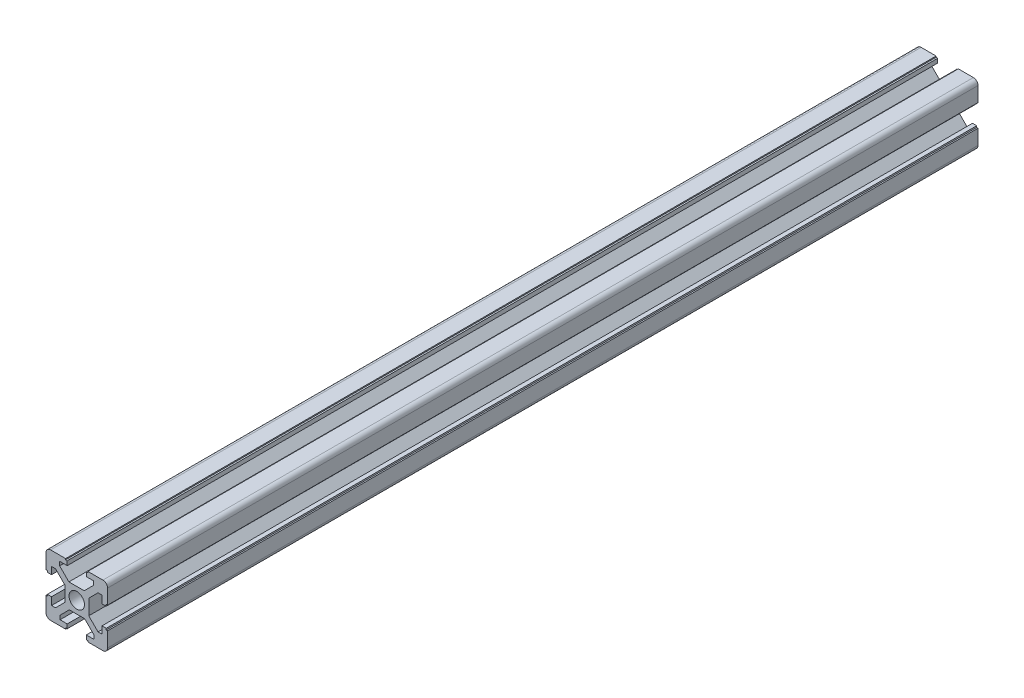
SolidWorks part; units mm, degrees
ref_plane "Front Plane" through (0, 0, 0) normal (0, 0, 1) x (1, 0, 0)
ref_plane "Top Plane" through (0, 0, 0) normal (0, 1, 0) x (1, 0, 0)
ref_plane "Right Plane" through (0, 0, 0) normal (1, 0, 0) x (0, 0, -1)
sketch "Sketch1" plane through (0, 0, 0) normal (0, 0, 1) x (1, 0, 0)
  line L0 (240.9169, 601.7923) -> (1204.5843, 601.7923) construction
  line L6 (13.0291, 10.3872) -> (13.0291, 12.8554)
  line L7 (12.7291, 6.0212) -> (29.7291, 6.0212)
  line L11 (11.2291, 7.5212) -> (11.2291, 24.3895)
  line L12 (12.7291, 25.8895) -> (29.7291, 25.8895)
  line L13 (31.2291, 7.5212) -> (31.2291, 24.3895)
  line L14 (11.2291, 6.0212) -> (31.2291, 25.8895) construction
  line L15 (11.2291, 25.8895) -> (31.2291, 6.0212) construction
  line L16 (13.0291, 24.0895) -> (13.041, 24.0895)
  line L17 (29.4291, 10.5205) -> (29.4291, 12.8554)
  line L18 (13.0291, 7.8212) -> (13.041, 7.8212)
  line L19 (11.2291, 15.9554) -> (31.2291, 15.9554) construction
  line L20 (11.6567, 12.8554) -> (13.0291, 12.8554)
  line L21 (11.6567, 19.0554) -> (13.0291, 19.0554)
  line L22 (21.2291, 6.0212) -> (21.2291, 25.8895) construction
  line L23 (24.8338, 25.9554) -> (24.8338, 25.5277)
  line L24 (17.3291, 21.0535) -> (17.3291, 19.8297)
  line L25 (11.2291, 19.56) -> (11.6567, 19.56)
  line L26 (11.6567, 19.56) -> (11.6567, 19.0554)
  line L27 (11.6567, 19.0554) -> (13.0291, 19.0554)
  line L28 (17.3291, 18.3778) -> (14.3166, 21.3903)
  line L29 (14.3166, 21.3903) -> (13.0291, 21.3903)
  line L30 (17.3291, 13.3997) -> (14.3166, 10.3872)
  line L31 (14.3166, 10.3872) -> (13.0291, 10.3872)
  line L32 (13.0291, 7.8212) -> (13.0291, 24.0895) construction
  line L33 (29.4172, 7.8212) -> (29.4291, 7.8212)
  line L34 (13.0291, 7.8212) -> (29.4291, 7.8212) construction
  line L35 (17.3291, 12.081) -> (17.3291, 10.641)
  line L36 (24.8338, 25.5277) -> (24.3291, 25.5277)
  line L37 (11.2291, 12.8554) -> (31.2291, 12.8554) construction
  line L38 (24.3291, 25.5277) -> (24.3291, 24.1554)
  line L39 (11.2291, 19.0554) -> (31.2291, 19.0554) construction
  line L40 (17.3291, 18.3778) -> (17.3291, 13.3997)
  line L41 (11.6567, 12.8554) -> (11.6567, 12.3367)
  line L42 (11.6567, 12.3367) -> (11.2291, 12.3367)
  line L43 (13.0291, 19.0554) -> (13.0291, 21.3903)
  line L44 (24.3291, 24.1554) -> (26.664, 24.1554)
  line L45 (26.664, 22.8679) -> (26.664, 24.1554)
  line L46 (23.6515, 19.8554) -> (26.664, 22.8679)
  line L47 (23.6515, 19.8554) -> (18.6734, 19.8554)
  line L48 (18.6734, 19.8554) -> (15.661, 22.8679)
  line L49 (15.661, 24.1554) -> (18.1291, 24.1554)
  line L50 (15.661, 22.8679) -> (15.661, 24.1554)
  line L51 (18.1291, 25.5277) -> (18.1291, 24.1554)
  line L52 (18.1291, 25.5277) -> (17.6104, 25.5277)
  line L53 (17.6104, 25.5277) -> (17.6104, 25.9554)
  line L54 (31.2291, 12.3507) -> (30.8015, 12.3507)
  line L55 (30.8015, 12.3507) -> (30.8015, 12.8554)
  line L56 (30.8015, 12.8554) -> (29.4291, 12.8554)
  line L57 (29.4291, 12.8554) -> (29.4291, 10.5205)
  line L58 (28.1416, 10.5205) -> (29.4291, 10.5205)
  line L59 (25.1291, 13.533) -> (28.1416, 10.5205)
  line L60 (25.1291, 13.533) -> (25.1291, 18.511)
  line L61 (25.1291, 18.511) -> (28.1416, 21.5235)
  line L62 (29.4291, 21.5235) -> (29.4291, 19.0554)
  line L63 (28.1416, 21.5235) -> (29.4291, 21.5235)
  line L64 (30.8015, 19.0554) -> (29.4291, 19.0554)
  line L65 (30.8015, 19.0554) -> (30.8015, 19.5741)
  line L66 (30.8015, 19.5741) -> (31.2291, 19.5741)
  line L67 (17.6244, 5.9554) -> (17.6244, 6.383)
  line L68 (17.6244, 6.383) -> (18.1291, 6.383)
  line L69 (18.1291, 6.383) -> (18.1291, 7.7554)
  line L70 (18.1291, 7.7554) -> (15.7942, 7.7554)
  line L71 (15.7942, 9.0429) -> (15.7942, 7.7554)
  line L72 (18.8067, 12.0554) -> (15.7942, 9.0429)
  line L73 (18.8067, 12.0554) -> (23.7848, 12.0554)
  line L74 (23.7848, 12.0554) -> (26.7973, 9.0429)
  line L75 (26.7973, 7.7554) -> (24.3291, 7.7554)
  line L76 (26.7973, 9.0429) -> (26.7973, 7.7554)
  line L77 (24.3291, 6.383) -> (24.3291, 7.7554)
  line L78 (24.3291, 6.383) -> (24.8478, 6.383)
  line L79 (24.8478, 6.383) -> (24.8478, 5.9554)
  line L80 (29.4172, 24.0895) -> (29.4291, 24.0895)
  line L81 (13.0291, 24.0895) -> (29.4291, 24.0895) construction
  line L82 (29.4291, 19.0554) -> (29.4291, 21.5235)
  line L83 (29.4291, 7.8212) -> (29.4291, 24.0895) construction
  circle A1 centre (21.2291, 15.9554) radius 2.5
  arc A2 (12.7291, 25.8895) -> (11.2291, 24.3895) centre (12.7291, 24.3895) ccw
  arc A3 (11.2291, 7.5212) -> (12.7291, 6.0212) centre (12.7291, 7.5212) ccw
  arc A4 (29.7291, 6.0212) -> (31.2291, 7.5212) centre (29.7291, 7.5212) ccw
  arc A5 (31.2291, 24.3895) -> (29.7291, 25.8895) centre (29.7291, 24.3895) ccw
  arc A6 (13.0291, 24.0895) -> (13.0291, 24.0895) centre (13.0291, 24.0895) ccw
  arc A7 (29.4291, 24.0895) -> (29.4291, 24.0895) centre (29.4291, 24.0895) ccw
  arc A8 (29.4291, 7.8212) -> (29.4291, 7.8212) centre (29.4291, 7.8212) ccw
  arc A9 (13.0291, 7.8212) -> (13.0291, 7.8212) centre (13.0291, 7.8212) ccw
  point P105 (21.2291, 15.9554)
  dimension "D1" = 20
  dimension "D2" = 1.5
  dimension "D3" = 1.5
  dimension "D7" = 4
  dimension "D8" = 6.1
  dimension "D4" = 1.8
  dimension "D5" = 3.1
  dimension "D6" = 3.1
extrude "Boss-Extrude1" add sketch "Sketch1" along normal blind 283 contours L13 A5 L12 L23 L36 L38 L44 L45 L46 L47 L48 L50 L49 L51 L52 L53 A2 L11 L25 L26 L21 L43 L29 L28 L40 L30 L31 L6 L20 L41 L42 region at (13.6729, 10.1053, 0)
